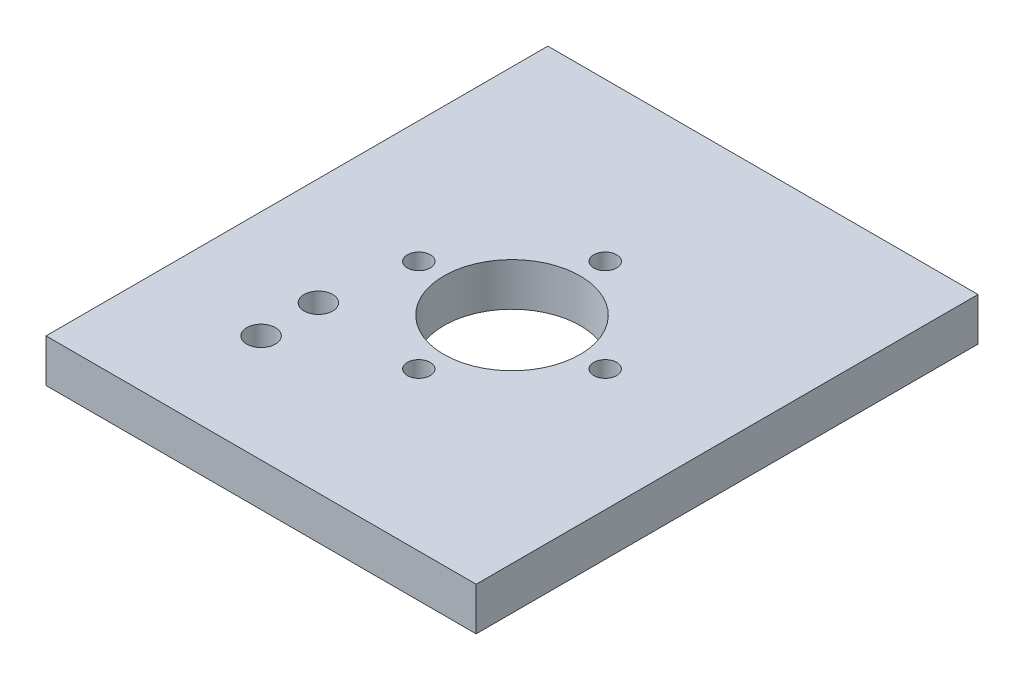
SolidWorks part; units mm, degrees
ref_plane "Front Plane" through (0, 0, 0) normal (0, 0, 1) x (1, 0, 0)
ref_plane "Top Plane" through (0, 0, 0) normal (0, 1, 0) x (1, 0, 0)
ref_plane "Right Plane" through (0, 0, 0) normal (1, 0, 0) x (0, 0, -1)
sketch "Sketch1" plane through (0, 0, 0) normal (0, 1, 0) x (1, 0, 0)
  line L0 (0, -55) -> (0, 55) construction
  line L1 (-30, 35) -> (30, 35)
  line L2 (-30, 35) -> (-30, -35)
  line L3 (-30, -35) -> (30, -35)
  line L4 (30, 35) -> (30, -35)
  line L5 (-30, 35) -> (30, -35) construction
  line L6 (-30, -35) -> (30, 35) construction
  line L7 (-55, 0) -> (55, 0) construction
  line L8 (-15, -20) -> (-15, -12) construction
  circle A0 centre (0, 0) radius 13 construction
  circle A1 centre (0, 13) radius 1.5 construction
  circle A2 centre (13, 0) radius 1.5 construction
  circle A3 centre (0, -13) radius 1.5 construction
  circle A4 centre (-13, 0) radius 1.5 construction
  circle A7 centre (0, 0) radius 9.5
  circle A8 centre (-17.5, 25) radius 2.5 construction
  circle A9 centre (17.5, 25) radius 2.5 construction
  circle A10 centre (17.5, -25) radius 2.5 construction
  circle A11 centre (-17.5, -25) radius 2.5 construction
  circle A12 centre (-50, 25) radius 2.5 construction
  circle A13 centre (-50, -25) radius 2.5 construction
  circle A14 centre (50, -25) radius 2.5 construction
  circle A15 centre (50, 25) radius 2.5 construction
  circle A16 centre (-15, -20) radius 2
  circle A17 centre (-15, -12) radius 2
  dimension "D1" = 26
  dimension "D2" = 3
  dimension "D4" = 19
  dimension "D7" = 5
  dimension "D10" = 5
  dimension "D13" = 8
  dimension "D15" = 15
  dimension "D16" = 4
  dimension "D5" = 17.5
  dimension "D6" = 60
  dimension "D8" = 70
  dimension "D9" = 25
  dimension "D11" = 50
  dimension "D12" = 25
  dimension "D14" = 15
  dimension "D3" = 4
extrude "Boss-Extrude1" add sketch "Sketch1" along normal blind 6
hole_wizard "CSK for M3 Flat Head Machine Screw1" positions "Sketch7" profile "Sketch8" countersink size "M3" standard "ANSI Metric" end condition through all
sketch "Sketch7" plane through (0, 0, 0) normal (0, -1, 0) x (-1, 0, 0)
  point P0 (-13, 0)
  point P3 (0, -13)
  point P6 (13, 0)
  point P9 (0, 13)
sketch "Sketch8" plane through (13, 0, 0) normal (1, 0, 0) x (0, 0, -1)
  line L0 (0, 0) -> (0, 6)
  line L1 (0, 6) -> (1.6, 6)
  line L2 (1.6, 6) -> (1.6, 1.55)
  line L3 (1.6, 1.55) -> (3.15, 0)
  line L5 (3.15, 0) -> (0, 0)
  line L6 (-1.6, 1.55) -> (-3.15, 0) construction
  line L11 (0, -6.35) -> (0, 107.95) construction
  dimension "Thru Hole Dia." = 3.2
  dimension "Thru Hole Depth" = 6
  dimension "Near C'Sink Dia." = 6.3
  dimension "Near C'Sink Angle" = 90
sketch "Sketch9" plane through (0, 0, 0) normal (0, 1, 0) x (1, 0, 0)
  line L0 (0, -55) -> (0, 55) construction
  line L1 (-55, 0) -> (55, 0) construction
  circle A0 centre (17.5, 25) radius 6
  circle A1 centre (-17.5, 25) radius 6
  circle A2 centre (-17.5, -25) radius 6
  circle A3 centre (17.5, -25) radius 6
  dimension "D1" = 12
equation "\"testbed_height\" = 91.50mm"
equation "\"plate_thickness\" = 6mm"
equation "\"main_body_splay_length\" = 48.5mm"
equation "\"splay_shaft_length_no_wires\" = 10mm"
equation "\"splay_shaft_length_wires\" = 6.5mm"
equation "\"timing_pulley_offset\" = 0mm"
equation "\"effective_motor_length\" = \"timing_pulley_offset\" + \"splay_shaft_length_no_wires\" + \"main_body_splay_length\""
equation "\"80_20_side\" = 25.4mm"
equation "\"80_20_length\" = 152.4mm"
equation "\"80_20_optic_mount_length\" = \"80_20_length\" - 25.4mm"
equation "\"optic_board_hole_size\" = 6.35mm"
equation "\"total_mounting_length\" = \"testbed_height\" - \"effective_motor_length\" - \"80_20_side\""
equation "\"mounting_vertical_portion_height\" = \"total_mounting_length\" - 2 * \"plate_thickness\""
equation "\"face_mount_width\" = 15.25mm"
equation "\"center_dist_to_face_mount_vertical_screws\" = 5mm"
equation "\"D1@Boss-Extrude1\"=\"plate_thickness\""
